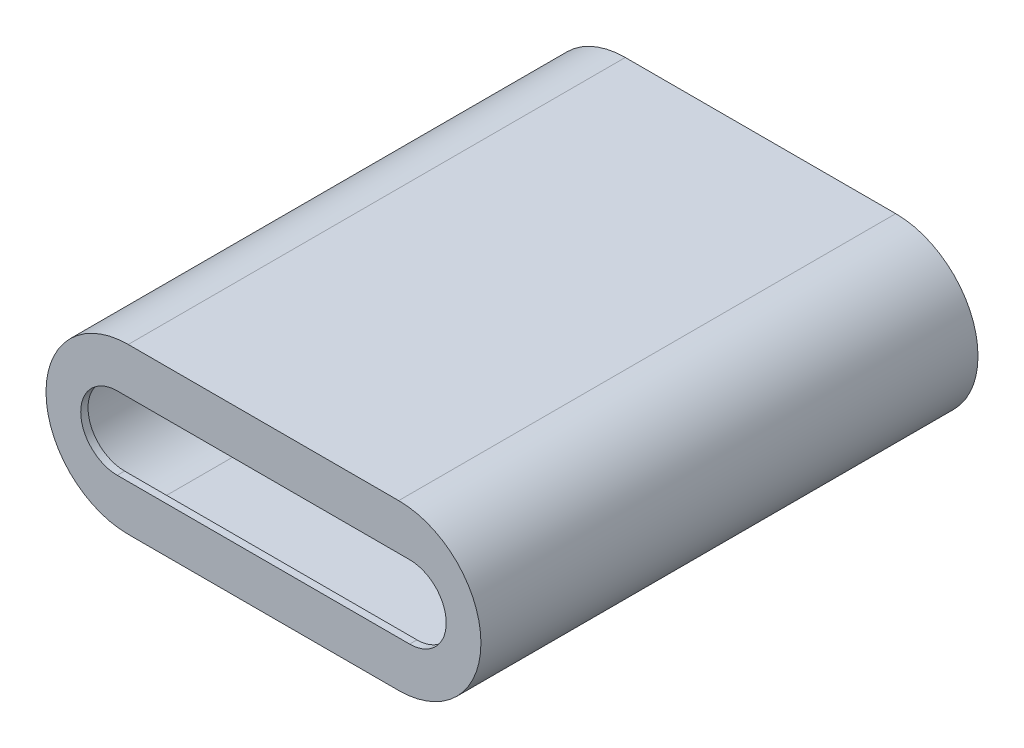
SolidWorks part; units mm, degrees
ref_plane "Front Plane" through (0, 0, 0) normal (0, 0, 1) x (1, 0, 0)
ref_plane "Top Plane" through (0, 0, 0) normal (0, 1, 0) x (1, 0, 0)
ref_plane "Right Plane" through (0, 0, 0) normal (1, 0, 0) x (0, 0, -1)
sketch "Sketch1" plane through (0, 0, 0) normal (0, 0, 1) x (1, 0, 0)
  line L0 (-18.5, 0) -> (18.5, 0) construction
  line L1 (-18.5, 9.25) -> (18.5, 9.25)
  line L2 (-18.5, -9.25) -> (18.5, -9.25)
  line L3 (-18.5, 11.25) -> (18.5, 11.25)
  line L4 (-18.5, -11.25) -> (18.5, -11.25)
  arc A0 (-18.5, 9.25) -> (-18.5, -9.25) centre (-18.5, 0) ccw
  arc A1 (18.5, -9.25) -> (18.5, 9.25) centre (18.5, 0) ccw
  arc A2 (18.5, -11.25) -> (18.5, 11.25) centre (18.5, 0) ccw
  arc A3 (-18.5, 11.25) -> (-18.5, -11.25) centre (-18.5, 0) ccw
  point P2 (0, 0)
  dimension "D1" = 9.25
  dimension "D2" = 37
  dimension "D3" = 2
extrude "Boss-Extrude1" add sketch "Sketch1" along normal mid plane 68
extrude "Boss-Extrude2" add sketch "Sketch1<2>" against normal blind 1 from surface contours L2 A1 L1 A0 region at (0, 0, 0) starting at face at (0, 0, 34)
sketch "Sketch1<2>" plane through (0, 0, 0) normal (0, 0, 1) x (1, 0, 0) same geometry as "Sketch1"
extrude "Boss-Extrude3" add sketch "Sketch1<3>" along normal blind 1 from surface contours L2 A1 L1 A0 region at (0, 0, 0) starting at face at (0, 0, -34)
sketch "Sketch1<3>" plane through (0, 0, 0) normal (0, 0, 1) x (1, 0, 0) same geometry as "Sketch1"
sketch "Sketch2" plane through (0, 0, 0) normal (0, 0, 1) x (1, 0, 0)
  line L0 (-20, 0) -> (20, 0) construction
  line L1 (-20, 5) -> (20, 5)
  line L2 (-20, -5) -> (20, -5)
  arc A0 (-20, 5) -> (-20, -5) centre (-20, 0) ccw
  arc A1 (20, -5) -> (20, 5) centre (20, 0) ccw
  point P2 (0, 0)
  dimension "D1" = 5
  dimension "D2" = 40
extrude "Cut-Extrude1" cut sketch "Sketch2" against normal through all both and the other way through all
sketch "Sketch3" plane through (0, 0, 0) normal (1, 0, 0) x (0, 0, -1)
  line L0 (0, 0) -> (0, 20.7532) construction
  line L1 (8, 13.25) -> (-8, 13.25)
  line L2 (8, 13.25) -> (8, 9.25)
  line L3 (8, 9.25) -> (-8, 9.25)
  line L4 (-8, 13.25) -> (-8, 9.25)
  line L5 (8, 13.25) -> (-8, 9.25) construction
  line L6 (8, 9.25) -> (-8, 13.25) construction
  line L7 (-34, 11.25) -> (34, 11.25) construction
  line L8 (32.725, 0) -> (-32.725, 0) construction
  line L9 (8, -9.25) -> (-8, -9.25)
  line L10 (8, -13.25) -> (8, -9.25)
  line L11 (8, -13.25) -> (-8, -13.25)
  line L12 (-8, -13.25) -> (-8, -9.25)
  point P0 (0, 11.25)
  point P8 (0, 0)
  point P9 (0, 0)
  dimension "D1" = 4
  dimension "D2" = 16
extrude "Cut-Extrude2" cut sketch "Sketch3" against normal through all both and the other way through all contours L12 L11 L10 L9 region at (0, -11.25, 0)
